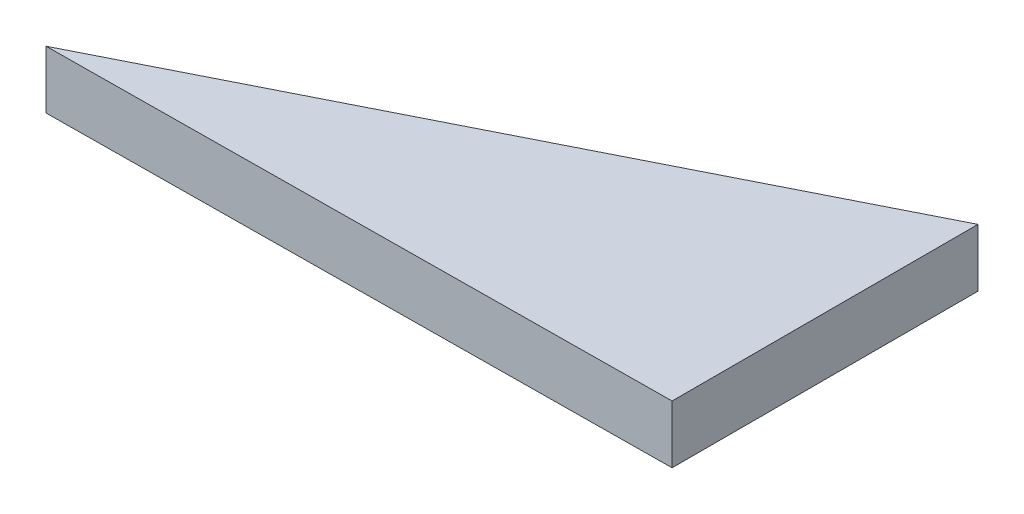
SolidWorks part; units mm, degrees
ref_plane "Front Plane" through (0, 0, 0) normal (0, 0, 1) x (1, 0, 0)
ref_plane "Top Plane" through (0, 0, 0) normal (0, 1, 0) x (1, 0, 0)
ref_plane "Right Plane" through (0, 0, 0) normal (1, 0, 0) x (0, 0, -1)
sketch "Sketch1" plane through (0, 0, 0) normal (0, 1, 0) x (1, 0, 0)
  line L1 (0, 0) -> (263.3435, 0)
  line L2 (0, 0) -> (0, 204.1914)
  line L3 (0, 204.1914) -> (263.3435, 204.1914)
  line L4 (263.3435, 0) -> (263.3435, 204.1914)
  line L5 (0, 0) -> (263.3435, 204.1914) construction
  line L6 (0, 204.1914) -> (263.3435, 0) construction
  point P4 (131.6717, 102.0957)
  dimension "D1" = 263.3435
  dimension "D2" = 204.1914
extrude "Boss-Extrude1" add sketch "Sketch1" along normal blind 4.6
sketch "Sketch3" plane through (0, 0, 0) normal (0, -1, 0) x (1, 0, 0)
  line L4 (214.0459, -75.9824) -> (188.3394, -104.2667)
  line L5 (188.3394, -104.2667) -> (162.4401, -75.7703)
  line L6 (188.1466, -47.486) -> (162.4401, -75.7703)
  line L7 (214.0459, -75.9824) -> (188.1466, -47.486)
  line L12 (263.3435, -100.7544) -> (122.1441, -256.1128)
  line L13 (263.3435, -76.442) -> (263.3435, -100.7544)
  line L14 (198.049, -4.6) -> (263.3435, -76.442)
  line L15 (263.3435, -76.442) -> (214.0459, -75.9824)
  line L16 (214.0459, -75.9824) -> (263.3435, -100.7544)
  line L17 (263.3435, -100.7544) -> (263.3435, -76.442)
  line M7 (263.3435, -204.1914) -> (263.3435, 0)
extrude "Cut-Extrude2" cut sketch "Sketch3" against normal through all flip side to cut contours L15 L16 M7 region at (246.911, 0, -84.3929)
equation "\"MDF\"= 4.8mm"
equation "\"Foamcore\"= 4.6mm"
equation "\"GMaterial\"= \"MDF\""
equation "\"PCB\" = 1.6mm"
equation "\"BaseWidth\" = 10in"
equation "\"SkidLength\" = 1in"
equation "\"SkidClearance\" = 0.4in"
equation "\"MotorMountLength\" = 2in"
equation "\"MotorMountWidth\" = \"GMaterial\""
equation "\"MotorMountHeight\" = 2.25in"
equation "\"UnoStackWidth\" = 77.4mm"
equation "\"UnoStackLength\" = 79.8mm"
equation "\"UnoStackHeight\" = 34.2mm"
equation "\"TallHexRiserHeight\" = 22.2mm"
equation "\"PingPongBallSize\" = 40mm"
equation "\"BarrelLength\" = 9in"
equation "\"BarrelSize\" = \"PingPongBallSize\""
equation "\"PlatformLength\" = 4in"
equation "\"PlatformWidth\" = 6in"
equation "\"WheelDiameter\"=2.99213"
equation "\"ServoMountHeight\"=2.49223"
equation "\"ServoGearHeight\" = 0.95330261in"
equation "\"ServoMountLength\"= 1.53774"
equation "\"PivotHoleRadius\"= 0.616358"
equation "\"PlatformMountHeight\" = 3.19"
equation "\"TensionOffSet\"= .3mm"
equation "\"MotorMountWedge\"=0.333333"
equation "\"LaserCutterOffset\"= .3mm"
equation "\"BumperWidth\"=11"
equation "\"PitcherWheelCompression\" = 2.5mm"
equation "\"BarrelToHopperDistance\" = 0.5405in"
equation "\"PitchingWheelWidth\" = 26.2mm"
equation "\"PitchingWheelDiameter\" = 65.5mm"
equation "\"PitchingWheelMountOffset\" = 8.4mm"
equation "\"PitchingWheelInnerDiameter\" = 45.5mm"
equation "\"PitchingWheelBoltShoulder\" = 4.5mm"
equation "\"BrassCouplingLength\" = 18mm"
equation "\"PitchingMotorHeight\" = 57.0mm"
equation "\"PitchingMotorShaftTopHeight\" = \"PitchingMotorHeight\" - 44.1mm"
equation "\"PitchingMotorBodyHeight\" = 38mm"
equation "\"PitchingMotorTopShoulderHeight\" = 40.6mm - \"PitchingMotorBodyHeight\" "
equation "\"PitchingMotorBottomShoulderHeight\" = 40.2mm - \"PitchingMotorBodyHeight\""
equation "\"PitchingMotorBottomShaftHeight\" = \"PitchingMotorHeight\" - \"PitchingMotorShaftTopHeight\" - \"PitchingMotorTopShoulderHeight\" - \"PitchingMotorBodyHeight\" - \"PitchingMotorBottomShoulderHeight\""
equation "\"PitchingMotorShaftDiameter\" = 2.2mm"
equation "\"PitchingMotorBodyDiameter\" = 27.4mm"
equation "\"PitchingMotorTopShoulderDiameter\" = 9.8mm"
equation "\"PitchingMotorBottomShoulderDiameter\" = 9.8mm"
equation "\"BrassCouplingHexSize\" = 12mm"
equation "\"BrassCouplingBoreSize\" = 3.17mm"
equation "\"PitchingMotorMountingHoleDistance\" = 16mm"
equation "\"Acrylic\" = 4.4mm"
equation "\"PitchingMotorDistance\" = \"PitchingWheelDiameter\" + \"PingPongBallSize\" - \"PitcherWheelCompression\"*2"
equation "\"PitchingMotorPlatformOffset\"=1"
equation "\"ServoPlatformOffset\"=1.64173"
equation "\"BallBearingDiameter\" = 22mm"
equation "\"BallBearingWidth\" = 9mm"
equation "\"BallBearingHexShoulder\" = 9mm - 5.9mm"
equation "\"BallBearingHexSize\" = .36in"
equation "\"PlatformMountFootLength\"=0.857143"
equation "\"WheelWidth\"= 26mm"
equation "\"ServoMountReductionBackHeight\"=2.25"
equation "\"PlatformBottomWidthThird\" =  0.857143in"
equation "\"PlatformMountBackReductionHeight\"= 2.5in"
equation "\"PlatformMountBackReductionWidth\"= 3/7in"
equation "\"PlatformMountFrontReductionWidth\" =  1.46226in"
equation "\"PlatformMountFrontReductionHeight\" = 2.5in"
equation "\"HopperLongWallLength\" = 8.646in"
equation "\"HopperShortWallLength\" = 0.9571in"
equation "\"HopperHeight\" = 3.50in - \"Foamcore\""
equation "\"HoperLongSlantLength\" = 7.064in"
equation "\"HopperBottomTemplateWidth\" = 8.03903165in"
equation "\"HopperBottomTemplateLength\" = 10.367854in"
equation "\"D1@Sketch1\"=\"HopperBottomTemplateLength\""
equation "\"D2@Sketch1\"=\"HopperBottomTemplateWidth\""
equation "\"D1@Boss-Extrude1\"=\"Foamcore\""
